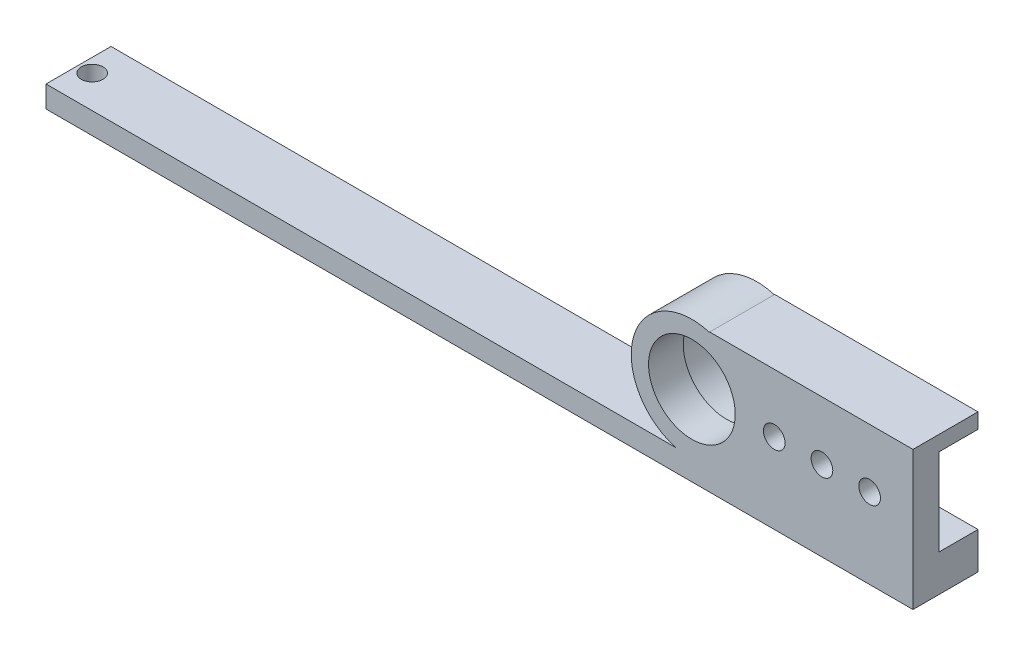
SolidWorks part; units mm, degrees
ref_plane "前视基准面" through (0, 0, 0) normal (0, 0, 1) x (1, 0, 0)
ref_plane "上视基准面" through (0, 0, 0) normal (0, 1, 0) x (1, 0, 0)
ref_plane "右视基准面" through (0, 0, 0) normal (1, 0, 0) x (0, 0, -1)
sketch "草图1" plane through (0, 0, 0) normal (0, 0, 1) x (1, 0, 0)
  line L1 (20, -10) -> (-20, -10)
  line L2 (20, -10) -> (20, 10)
  line L3 (20, 10) -> (-20, 10)
  line L4 (-20, -10) -> (-20, 10)
  line L5 (20, -10) -> (-20, 10) construction
  line L6 (20, 10) -> (-20, -10) construction
  point P0 (0, 0)
  dimension "D1" = 40
  dimension "D2" = 20
extrude "凸台-拉伸1" add sketch "草图1" along normal blind 6
sketch "草图2" plane through (0, 0, 6) normal (0, 0, 1) x (1, 0, 0)
  line L0 (20, -10) -> (20, 10) construction
  circle A0 centre (10, 0) radius 2.5
  circle A1 centre (-1, 0) radius 2.5
  circle A2 centre (-12, 0) radius 2.5
  dimension "D1" = 10
  dimension "D2" = 5
  dimension "D3" = 3
extrude "切除-拉伸1" cut sketch "草图2" against normal through all
sketch "草图3" plane through (0, 0, 6) normal (0, 0, 1) x (1, 0, 0)
  line L0 (20, 13.5) -> (20, 10)
  line L1 (20, -13.5) -> (-26.894, -13.5)
  line L3 (20, 13.5) -> (-26.894, 13.5)
  line L4 (-20, 10) -> (-20, -10)
  line L5 (-20, -10) -> (20, -10)
  line L6 (20, -10) -> (20, 10)
  line L7 (20, 10) -> (-20, 10)
  line L8 (-20, 10) -> (-20, -10)
  line L9 (-20, -10) -> (20, -10)
  line L10 (20, -10) -> (20, 10)
  line L11 (20, 10) -> (-20, 10)
  line L12 (-26.894, -13.5) -> (-26.894, 13.5)
  line L13 (20, -10.0394) -> (-26.894, 13.5) construction
  line L14 (20, 10.0394) -> (-26.894, -13.5) construction
  line L15 (20, -10) -> (20, -13.5)
  circle A0 centre (-31, 0) radius 11
  circle A1 centre (-31, 0) radius 14
  point P2 (0, 0)
  line M10 (-20, 10) -> (-20, -10)
  line M11 (-20, -10) -> (20, -10)
  line M13 (20, 10) -> (-20, 10)
  dimension "D3" = 22
  dimension "D4" = 28
  dimension "D2" = 3.5
  dimension "D1" = 0
extrude "凸台-拉伸2" add sketch "草图3" against normal blind 15 contours L3 A1 L1 L12 A0 | A1 L1 L15 M11 M10 | L1 A1 L8 A0 L12 | L8 A1 L3 L12 A0 | L8 A1 | A1 L0 L3 M10 M13 region at (-1.9449, 11.7771, 6) region at (-1.9449, -11.7771, 6) region at (-23.0173, 9.0328, 6) region at (-27.2274, 11.7946, 6) region at (-18.7882, 0, 6) region at (-23.0173, -9.0328, 6)
sketch "草图5" plane through (0, 0, 6) normal (0, 0, 1) x (1, 0, 0)
  circle A0 centre (-31, 0) radius 10
  circle A1 centre (-31, 0) radius 11 construction
  circle A2 centre (-31, 0) radius 11
  dimension "D1" = 20
extrude "凸台-拉伸3" add sketch "草图5" against normal blind 8
sketch "草图6" plane through (0, 0, 6) normal (0, 0, 1) x (1, 0, 0)
  circle A0 centre (-31, 0) radius 8.5
  circle A1 centre (-31, 0) radius 10 construction
  circle A2 centre (-31, 0) radius 10
  dimension "D1" = 17
sketch "草图9" plane through (0, -13.5, 0) normal (0, -1, 0) x (1, 0, 0)
  circle A0 centre (-18.2368, -1.344) radius 5.5352
sketch "草图10" plane through (20, 0, 0) normal (1, 0, 0) x (0, 0, -1)
  line L1 (9, -13.5) -> (-6, -13.5)
  line L2 (9, -13.5) -> (9, -18.5)
  line L3 (9, -18.5) -> (-6, -18.5)
  line L4 (-6, -13.5) -> (-6, -18.5)
  dimension "D1" = 5
extrude "凸台-拉伸4" add sketch "草图10" against normal blind 200
sketch "草图11" plane through (0, 0, 6) normal (0, 0, 1) x (1, 0, 0)
  line L1 (-28.6193, -11.8661) -> (-25.5243, -11.8661)
  line L2 (-28.6193, -11.8661) -> (-28.6193, -14.961)
  line L3 (-28.6193, -14.961) -> (-25.5243, -14.961)
  line L4 (-25.5243, -11.8661) -> (-25.5243, -14.961)
extrude "凸台-拉伸5" add sketch "草图11" against normal through all
sketch "草图13" plane through (0, -18.5, 0) normal (0, -1, 0) x (1, 0, 0)
  line L0 (-186.8528, 6) -> (-186.8528, -9)
  line L1 (-180, 6) -> (20, 6) construction
  line L2 (-186.8528, 80.0936) -> (-186.8528, -289.9064) construction
  line L3 (-180, -9) -> (20, -9) construction
sketch "草图14" plane through (0, -18.5, 0) normal (0, -1, 0) x (1, 0, 0)
  line L0 (-118.4338, -15.7251) -> (-118.4338, 9.3691)
  line L1 (-118.4338, 126.7017) -> (-118.4338, -243.2983) construction
sketch "草图15" plane through (0, -18.5, 0) normal (0, -1, 0) x (1, 0, 0)
  line L1 (-118.4338, -15.7251) -> (-184.1416, -15.7251)
  line L2 (-118.4338, -15.7251) -> (-118.4338, 11.9644)
  line L3 (-118.4338, 11.9644) -> (-184.1416, 11.9644)
  line L4 (-184.1416, -15.7251) -> (-184.1416, 11.9644)
sketch "草图16" plane through (0, -18.5, 0) normal (0, -1, 0) x (1, 0, 0)
  line L0 (-186.8528, 6.4407) -> (-186.8528, -38.9947)
  line L1 (-186.8528, 80.0936) -> (-186.8528, -289.9064) construction
sketch "草图17" plane through (0, -18.5, 0) normal (0, -1, 0) x (1, 0, 0)
  line L0 (-186.8528, 7.3332) -> (-186.8528, -35.3686)
  line L1 (-186.8528, 80.0936) -> (-186.8528, -289.9064) construction
sketch "草图18" plane through (0, -18.5, 0) normal (0, -1, 0) x (1, 0, 0)
  line L1 (-186.8528, -38.9947) -> (-206.846, -38.9947)
  line L2 (-186.8528, -38.9947) -> (-186.8528, 25.1925)
  line L3 (-186.8528, 25.1925) -> (-206.846, 25.1925)
  line L4 (-206.846, -38.9947) -> (-206.846, 25.1925)
extrude "切除-拉伸3" cut sketch "草图18" against normal through all rebuild error yes
sketch "草图19" plane through (0, -18.5, 0) normal (0, -1, 0) x (1, 0, 0)
  line L0 (-186.8528, 6) -> (-186.8528, -9)
  line L1 (-186.8528, -1.5) -> (-176.8528, -1.5) construction
  circle A0 centre (-176.8528, -1.5) radius 2.5
  dimension "D2" = 5
  dimension "D1" = 10
extrude "切除-拉伸4" cut sketch "草图19" against normal blind 10 contours A0 region at (-176.8528, -18.5, -1.5)
